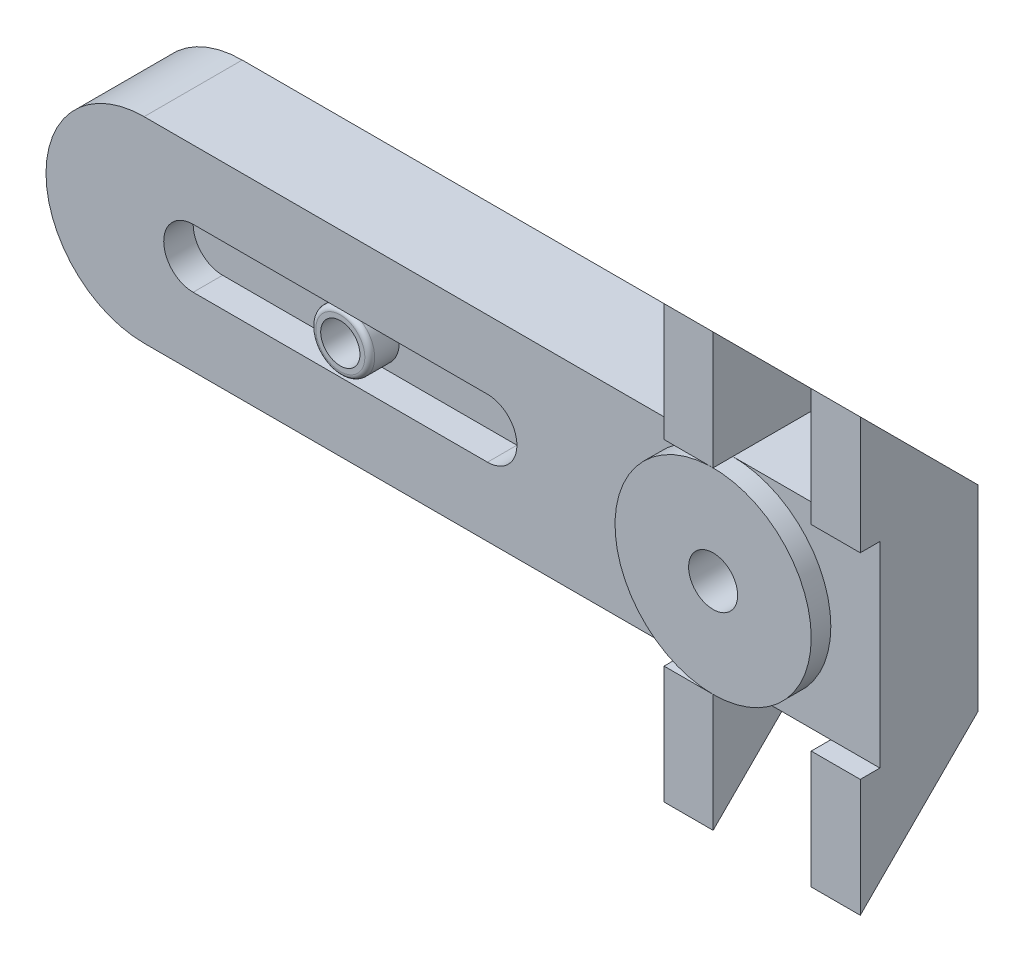
SolidWorks part; units mm, degrees
ref_plane "Front Plane" through (0, 0, 0) normal (0, 0, 1) x (1, 0, 0)
ref_plane "Top Plane" through (0, 0, 0) normal (0, 1, 0) x (1, 0, 0)
ref_plane "Right Plane" through (0, 0, 0) normal (1, 0, 0) x (0, 0, -1)
sketch "Sketch1" plane through (0, 0, 0) normal (0, 0, 1) x (1, 0, 0)
  line L0 (-33.1481, 2.2715) -> (-3.1481, 2.2715) construction
  line L1 (-33.1481, 5.2715) -> (-3.1481, 5.2715)
  line L2 (-33.1481, -0.7285) -> (-3.1481, -0.7285)
  arc A0 (-33.1481, 5.2715) -> (-33.1481, -0.7285) centre (-33.1481, 2.2715) ccw
  arc A1 (-3.1481, -0.7285) -> (-3.1481, 5.2715) centre (-3.1481, 2.2715) ccw
  circle A2 centre (-18.1481, 2.2715) radius 2
  point P2 (-18.1481, 2.2715)
  dimension "D3" = 4
  dimension "D1" = 30
  dimension "D2" = 6
extrude "Boss-Extrude1" add sketch "Sketch1" along normal blind 2
sketch "Sketch2" plane through (0, 0, 2) normal (0, 0, 1) x (1, 0, 0)
  circle A0 centre (-18.1481, 2.2715) radius 2
  circle A1 centre (-18.1481, 2.2715) radius 3
extrude "Boss-Extrude2" add sketch "Sketch2" along normal blind 3
fillet "Fillet1" radius 0.5 1 edges at (-15.1481, 2.2715, 5) type face fillet first side face at (-15.1481, 2.2715, 5) second side face at (-15.1481, 2.2715, 5)
sketch "Sketch4" plane through (0, 0, 0) normal (0, 0, -1) x (-1, 0, 0)
  line L1 (48.1481, 12.2715) -> (-41.8519, 12.2715)
  line L2 (48.1481, 12.2715) -> (48.1481, -7.7285)
  line L3 (48.1481, -7.7285) -> (-41.8519, -7.7285)
  line L4 (-41.8519, 12.2715) -> (-41.8519, -7.7285)
  circle A0 centre (18.1481, 2.2715) radius 2 construction
  arc M1 (33.1481, -0.7285) -> (33.1481, 5.2715) centre (33.1481, 2.2715) ccw
  line M2 (33.1481, 5.2715) -> (3.1481, 5.2715)
  arc M3 (3.1481, 5.2715) -> (3.1481, -0.7285) centre (3.1481, 2.2715) ccw
  line M4 (3.1481, -0.7285) -> (33.1481, -0.7285)
  dimension "D2" = 10
  dimension "D1" = 20
  dimension "D3" = 90
  dimension "D4" = 30
extrude "Boss-Extrude3" add sketch "Sketch4" against normal blind 5 separate body contours L1 L4 L3 L2 M1 M4 M3 M2 region at (-47.2262, 2.2715, 0)
sketch "Sketch5" plane through (0, 0, 0) normal (0, 0, -1) x (-1, 0, 0)
  line L1 (-41.8519, 12.2715) -> (48.1481, 12.2715)
  line L2 (-41.8519, 12.2715) -> (-41.8519, -7.7285)
  line L3 (-41.8519, -7.7285) -> (48.1481, -7.7285)
  line L4 (48.1481, 12.2715) -> (48.1481, -7.7285)
extrude "Boss-Extrude6" add sketch "Sketch5" along normal blind 5 separate body
fillet "Fillet3" radius 10 1 edges at (-48.1481, -7.7285, 2.5) type face fillet first side face at (-3.1481, -7.7285, 2.5) second side face at (-48.1481, 2.2715, 2.5)
fillet "Fillet4" radius 10 1 edges at (-48.1481, -7.7285, -2.5) type face fillet first side face at (-3.1481, -7.7285, -2.5) second side face at (-48.1481, 2.2715, -2.5)
fillet "Fillet5" radius 10 1 edges at (-48.1481, 12.2715, -2.5) type face fillet first side face at (-48.1481, 7.2715, -2.5) second side face at (-3.1481, 12.2715, -2.5)
fillet "Fillet6" radius 10 1 edges at (-48.1481, 12.2715, 2.5) type face fillet first side face at (-48.1481, 7.2715, 2.5) second side face at (-3.1481, 12.2715, 2.5)
sketch "Sketch6" plane through (0, 0, 5) normal (0, 0, 1) x (1, 0, 0)
  line L0 (-18.1481, 2.2715) -> (21.8519, 2.2715)
  dimension "D1" = 40
sketch "Sketch7" plane through (0, 0, 5) normal (0, 0, 1) x (1, 0, 0)
  circle A0 centre (21.8519, 2.2715) radius 2.5
  dimension "D1" = 5
extrude "Cut-Extrude1" cut sketch "Sketch7" against normal blind 10
sketch "Sketch8" plane through (0, 0, 5) normal (0, 0, 1) x (1, 0, 0)
  circle A0 centre (21.8519, 2.2715) radius 2.5
  circle A1 centre (21.8519, 2.2715) radius 10
extrude "Boss-Extrude7" add sketch "Sketch8" along normal blind 2
sketch "Sketch9" plane through (0, 0, 5) normal (0, 0, 1) x (1, 0, 0)
  line L0 (21.8519, -7.7285) -> (41.8519, -7.7285) construction
  line L1 (41.8519, 12.2715) -> (36.8519, 12.2715)
  line L2 (41.8519, 12.2715) -> (41.8519, -7.7285)
  line L3 (41.8519, -7.7285) -> (36.8519, -7.7285)
  line L4 (36.8519, 12.2715) -> (36.8519, -7.7285)
  dimension "D1" = 5
extrude "Cut-Extrude2" cut sketch "Sketch9" against normal blind 10
sketch "Sketch10" plane through (36.8519, 0, 0) normal (1, 0, 0) x (0, 0, -1)
  line L0 (5, 12.2715) -> (-7, 12.2715)
  line L1 (-7, 12.2715) -> (-7, -7.7285) construction
  line L2 (-7, 12.2715) -> (-7, 24.2715)
  line L3 (-7, 24.2715) -> (5, 12.2715)
  line L4 (5, -7.7285) -> (-7, -7.7285)
  line L5 (-7, -7.7285) -> (-7, -19.7285)
  line L6 (-7, -19.7285) -> (5, -7.7285)
  dimension "D1" = 12
  dimension "D2" = 12
  dimension "D3" = 90
extrude "Boss-Extrude8" add sketch "Sketch10" against normal blind 5
sketch "Sketch11" plane through (0, 0, 7) normal (0, 0, 1) x (1, 0, 0)
  line L0 (21.8519, -7.7285) -> (31.8519, -7.7285) construction
  line L1 (16.8519, 24.2715) -> (21.8519, 24.2715)
  line L2 (16.8519, 24.2715) -> (16.8519, 12.2715)
  line L3 (16.8519, 12.2715) -> (21.8519, 12.2715)
  line L4 (21.8519, 24.2715) -> (21.8519, 12.2715)
  line L5 (16.8519, -19.7285) -> (21.8519, -19.7285)
  line L6 (16.8519, -19.7285) -> (16.8519, -7.7285)
  line L7 (16.8519, -7.7285) -> (21.8519, -7.7285)
  line L8 (21.8519, -19.7285) -> (21.8519, -7.7285)
  line L9 (36.8519, -7.7285) -> (36.8519, -19.7285) construction
  line L10 (21.8519, 12.2715) -> (31.8519, 12.2715) construction
  line L11 (36.8519, 24.2715) -> (36.8519, 12.2715) construction
  circle A0 centre (21.8519, 2.2715) radius 10 construction
  arc A1 (21.8519, -7.7285) -> (21.8519, 12.2715) centre (21.8519, 2.2715) ccw construction
  dimension "D1" = 12
  dimension "D2" = 0
  dimension "D3" = 5
  dimension "D4" = 20
  dimension "D5" = 0
  dimension "D6" = 12
  dimension "D7" = 5
  dimension "D8" = 20
extrude "Boss-Extrude9" add sketch "Sketch11" against normal blind 12 separate body
sketch "Sketch12" plane through (21.8519, 0, 0) normal (1, 0, 0) x (0, 0, -1)
  line L0 (-7, 24.2715) -> (5, 24.2715)
  line L1 (5, 24.2715) -> (5, 12.2715)
  line L2 (5, 12.2715) -> (-7, 24.2715)
  line L3 (5, -7.7285) -> (5, -19.7285)
  line L4 (5, -19.7285) -> (-7, -19.7285)
  line L5 (-7, -19.7285) -> (5, -7.7285) construction
  line L6 (-7, -19.7285) -> (5, -7.7285)
extrude "Cut-Extrude3" cut sketch "Sketch12" against normal blind 12
